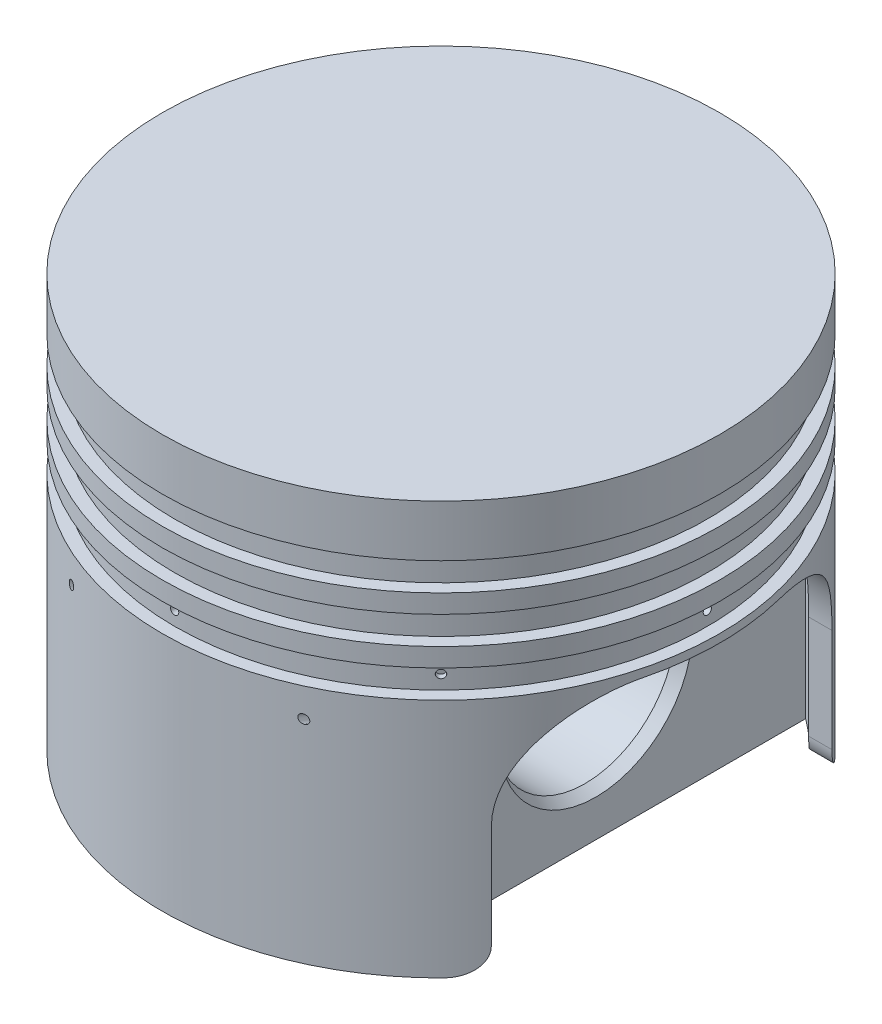
SolidWorks part; units mm, degrees
note: '?' marks a value the reader was unsure of.
material "Aluminum, EN AC-44300, die cast, F"
ref_plane "Front Plane" through (0, 0, 0) normal (0, 0, 1) x (1, 0, 0)
ref_plane "Top Plane" through (0, 0, 0) normal (0, 1, 0) x (1, 0, 0)
ref_plane "Right Plane" through (0, 0, 0) normal (1, 0, 0) x (0, 0, -1)
sketch "Sketch4" plane through (0, 0, 0) normal (0, 0, 1) x (1, 0, 0)
  line L0 (0, 0) -> (0, -9.13)
  line L1 (0, -9.13) -> (50.5, -9.13)
  line L2 (50.5, -9.13) -> (50.5, -80)
  line L3 (50.5, -80) -> (54, -80)
  line L4 (54, -80) -> (54, 0)
  line L5 (54, 0) -> (0, 0)
  dimension "D1" = 54
  dimension "D2" = 80
  dimension "D3" = 9.13
  dimension "D4" = 3.5
revolve "Revolve2" add sketch "Sketch4" angle 360 about L0
sketch "Sketch5" plane through (0, 0, 0) normal (1, 0, 0) x (0, 0, -1)
  line L0 (-54, -80) -> (54, -80) construction
  line L1 (-33, -80) -> (33, -80)
  line L2 (-33, -80) -> (-33, -35)
  line L3 (-33, -35) -> (33, -35)
  line L4 (33, -80) -> (33, -35)
  line L5 (-33, -80) -> (33, -35) construction
  line L6 (-33, -35) -> (33, -80) construction
  point P0 (0, -57.5)
  dimension "D1" = 66
  dimension "D2" = 45
extrude "Cut-Extrude2" cut sketch "Sketch5" against normal through all both and the other way through all
sketch "Sketch6" plane through (0, 0, 0) normal (1, 0, 0) x (0, 0, -1)
  line L0 (0, 0) -> (0, -25.257) construction
  line L1 (54, -80) -> (54, 0) construction
  line L2 (51.6, -15.4) -> (56.4, -15.4)
  line L3 (51.6, -15.4) -> (51.6, -10)
  line L4 (51.6, -10) -> (56.4, -10)
  line L5 (56.4, -15.4) -> (56.4, -10)
  line L6 (51.6, -15.4) -> (56.4, -10) construction
  line L7 (51.6, -10) -> (56.4, -15.4) construction
  line L8 (54, 0) -> (-54, 0) construction
  point P3 (54, -12.7)
  dimension "D2" = 2.4
  dimension "D3" = 10
revolve "Cut-Revolve2" cut sketch "Sketch6" angle 360 about L0
pattern_linear "LPattern2" count 2 spacing 9 along (0, -1, 0) of "Cut-Revolve2"
fillet "Fillet1" radius 20 4 edges at (40.4849, -35, 33) (-40.4849, -35, 33) (-40.4849, -35, -33) (40.4849, -35, -33)
ref_plane "Plane1" through (0, 0, 55) normal (0, 0, 1) x (1, 0, 0)
pattern_linear "LPattern4" count 2 spacing 9 along (0, -1, 0) of "LPattern2"
ref_plane "Plane3" through (0, 0, 47) normal (0, 0, 1) x (1, 0, 0)
sketch "Sketch19" plane through (0, -9.13, 0) normal (0, -1, 0) x (1, 0, 0)
  line L0 (0, 36.8121) -> (0, -30.3191) construction
  line L1 (30, 25) -> (15, 25)
  line L2 (-30, -25) -> (-15, -25)
  line L3 (-30, -25) -> (-30, 25)
  line L4 (-30, 25) -> (-15, 25)
  line L5 (-15, -25) -> (-15, 25)
  line L6 (-30, -25) -> (-15, 25) construction
  line L7 (-30, 25) -> (-15, -25) construction
  line L8 (15, -25) -> (15, 25)
  line L9 (30, -25) -> (15, -25)
  line L10 (30, -25) -> (30, 25)
  line L11 (-30, 25) -> (-30, 40.6233)
  line L12 (-15, 25) -> (-15, 48.2208)
  line L13 (-30, -25) -> (-30, -40.6233)
  line L14 (-15, -25) -> (-15, -48.2208)
  line L15 (15, 25) -> (15, 48.2208)
  line L16 (30, 25) -> (30, 40.6233)
  line L17 (30, -25) -> (30, -40.6233)
  line L18 (15, -25) -> (15, -48.2208)
  circle A0 centre (0, 0) radius 50.5 construction
  circle A1 centre (0, 0) radius 50.5
  point P3 (-22.5, 0)
  circle M11 centre (0, 0) radius 50.5
  dimension "D1" = 50
  dimension "D2" = 15
  dimension "D3" = 15
extrude "Boss-Extrude3" add sketch "Sketch19" along normal up to surface (70.87 mm away) contours L4 L12 L11 M11 | L2 L5 L4 L3 | L14 L2 L13 M11 | L1 L16 L15 M11 | L9 L10 L1 L8 | L9 L18 L17 M11 up to face at (0, -80, 42.625)
sketch "Sketch20" plane through (-30, 0, 0) normal (-1, 0, 0) x (0, 0, 1)
  line L4 (40.6233, -80) -> (-40.6233, -80) construction
  circle A0 centre (0, -54.13) radius 17.5
  dimension "D1" = 35
  dimension "D3" = 25.87
extrude "Cut-Extrude4" cut sketch "Sketch20" against normal through all
fillet "Fillet8" radius 5 4 edges at (-40.4849, -80, -33) (40.4849, -80, -33) (40.4849, -80, 33) (-40.4849, -80, 33)
sketch "Sketch22" plane through (0, 0, 47) normal (0, 0, 1) x (1, 0, 0)
  point P6 (0, -30.7)
hole_wizard "1/16 (0.0625) Diameter Hole3" positions "Sketch22" profile "Sketch23" hole size "1/16" standard "ANSI Inch"
sketch "Sketch23" plane through (0, -30.7, 47) normal (1, 0, 0) x (0, 1, 0)
  line L0 (0, 0) -> (0, 4.6)
  line L1 (0, 4.6) -> (0.7937, 4.6)
  line L2 (0.7937, 4.6) -> (0.7937, 0.635)
  line L3 (0.7937, 0.635) -> (1.4287, 0)
  line L5 (1.4287, 0) -> (0, 0)
  line L6 (-0.7937, 0.635) -> (-1.4287, 0) construction
  line L11 (0, -6.35) -> (0, 107.95) construction
  dimension "Thru Hole Dia." = 1.5875
  dimension "Thru Hole Depth" = 4.6
  dimension "Near C'Sink Dia." = 2.8575
  dimension "Near C'Sink Angle" = 90
pattern_circular "CirPattern3" count 8 over 360 about axis through (0, -18, 0) along (0, 1, 0) of "1/16 (0.0625) Diameter Hole3"
ref_plane "Plane9" through (0, 0, 17.5) normal (0, 0, 1) x (1, 0, 0)
sketch "Sketch39" plane through (0, 0, 17.5) normal (0, 0, 1) x (1, 0, 0)
  point P8 (22.5, -51.4441)
ref_plane "Plane10" through (0, 0, 54) normal (0, 0, 1) x (1, 0, 0)
sketch "Sketch40" plane through (0, 0, 54) normal (0, 0, 1) x (1, 0, 0)
  line L0 (0, 0) -> (0, -37) construction
  line L1 (0, -37) -> (22.5, -37) construction
  point P3 (-22.5, -37)
  point P5 (22.5, -37)
  dimension "D1" = 37
ref_axis "Axis2" through (22.5, -51.4441, 17.5) along (0, 0.368, 0.9298)?
ref_plane "Plane11" through (22.5, -37, 54) normal (0, 0.368, 0.9298) x (1, 0, 0)
sketch "Sketch42" plane through (22.5, -37, 54) normal (0, 0.368, 0.9298) x (1, 0, 0)
  circle A0 centre (0, 0) radius 0.8
  dimension "D1" = 1.6
extrude "Cut-Extrude5" cut sketch "Sketch42" against normal blind 50
mirror "Mirror1" about plane through (0, 0, 0) normal (1, 0, 0) of "Cut-Extrude5"
mirror "Mirror2" about plane through (0, 0, 0) normal (0, 0, 1) of "Mirror1", "Cut-Extrude5"
fillet "Fillet4" radius 4 4 edges at (-30, -9.13, 0) (30, -9.13, 0) (50.5, -9.13, 0) (-50.5, -9.13, 0)
fillet "Fillet18" radius 8 4 edges at (0, -9.13, -50.5) (0, -9.13, 50.5) (15, -9.13, 0) (-15, -9.13, 0)
chamfer "Chamfer2" distance 2.1 angle 30 4 edges at (-15, -71.63, 0) (-30, -71.63, 0) (15, -71.63, 0) (30, -71.63, 0)
equation "\"piston crown\"= 9.13mm"
equation "\"D3@Sketch4\"=\"piston crown\""
equation "\"Crank Radius\"= 5.33mm"
equation "\"Journal Radius\"= 31.75mm"
equation "\"Counterweight Thickness\"= 10mm"
equation "\"Bore\"= 108mm"
equation "\"Stroke\"= 86.4mm"
equation "\"t1\"= 2.4mm"
equation "\"t2\"= 5.4mm"
equation "\"b1\"= 10mm"
equation "\"b2\"= 4.7mm"
equation "\"t3\"= 5.0mm"
equation "\"t4\"= 1.5mm"
equation "\"D1@Sketch4\"=\"Bore\"/2"
equation "\"D1@Sketch6\"=\"t2\""
equation "\"D3@Sketch6\"=\"b1\""
